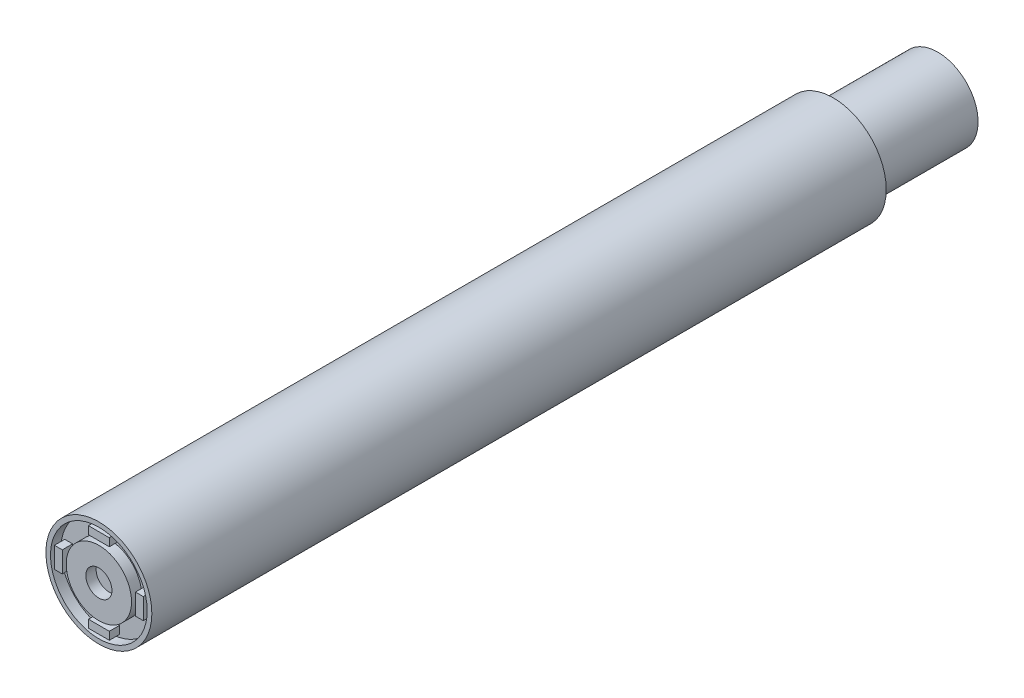
SolidWorks part; units mm, degrees
ref_plane "Front Plane" through (0, 0, 0) normal (0, 0, 1) x (1, 0, 0)
ref_plane "Top Plane" through (0, 0, 0) normal (0, 1, 0) x (1, 0, 0)
ref_plane "Right Plane" through (0, 0, 0) normal (1, 0, 0) x (0, 0, -1)
sketch "Sketch1" plane through (0, 0, 0) normal (0, 0, 1) x (1, 0, 0)
  circle A0 centre (0, 0) radius 2.575
extrude "Boss-Extrude1" add sketch "Sketch1" against normal blind 35.7
sketch "Sketch2" plane through (0, 0, 0) normal (0, 0, 1) x (1, 0, 0)
  circle A0 centre (0, 0) radius 2.35
extrude "Cut-Extrude1" cut sketch "Sketch2" against normal blind 0.5
sketch "Sketch5" plane through (0, 0, 0) normal (0, 0, 1) x (1, 0, 0)
  circle A0 centre (0, 0) radius 0.635
  circle A1 centre (0, 0) radius 1.5875
  dimension "D1" = 1.27
extrude "Boss-Extrude2" add sketch "Sketch5" against normal blind 0.508
sketch "Sketch6" plane through (0, 0, 0) normal (0, 0, 1) x (1, 0, 0)
  line L1 (-0.508, 1.778) -> (0.508, 1.778)
  line L2 (-0.508, 1.778) -> (-0.508, 2.159)
  line L3 (-0.508, 2.159) -> (0.508, 2.159)
  line L4 (0.508, 1.778) -> (0.508, 2.159)
  line L5 (-0.508, 1.778) -> (0.508, 2.159) construction
  line L6 (-0.508, 2.159) -> (0.508, 1.778) construction
  line L7 (-0.508, -2.159) -> (0.508, -2.159)
  line L8 (-0.508, -2.159) -> (-0.508, -1.778)
  line L9 (-0.508, -1.778) -> (0.508, -1.778)
  line L10 (0.508, -2.159) -> (0.508, -1.778)
  line L11 (-0.508, -2.159) -> (0.508, -1.778) construction
  line L12 (-0.508, -1.778) -> (0.508, -2.159) construction
  line L13 (-2.159, -0.508) -> (-1.778, -0.508)
  line L14 (-2.159, -0.508) -> (-2.159, 0.508)
  line L15 (-2.159, 0.508) -> (-1.778, 0.508)
  line L16 (-1.778, -0.508) -> (-1.778, 0.508)
  line L17 (-2.159, -0.508) -> (-1.778, 0.508) construction
  line L18 (-2.159, 0.508) -> (-1.778, -0.508) construction
  line L19 (1.778, -0.508) -> (2.159, -0.508)
  line L20 (1.778, -0.508) -> (1.778, 0.508)
  line L21 (1.778, 0.508) -> (2.159, 0.508)
  line L22 (2.159, -0.508) -> (2.159, 0.508)
  line L23 (1.778, -0.508) -> (2.159, 0.508) construction
  line L24 (1.778, 0.508) -> (2.159, -0.508) construction
  point P0 (0, 1.9685)
  point P8 (0, -1.9685)
  point P13 (-1.9685, 0)
  point P18 (1.9685, 0)
  dimension "D1" = 1.016
  dimension "D2" = 0.381
  dimension "D3" = 1.016
  dimension "D4" = 0.381
  dimension "D5" = 1.016
  dimension "D6" = 0.381
  dimension "D7" = 1.016
  dimension "D8" = 0.381
extrude "Boss-Extrude3" add sketch "Sketch6" against normal blind 0.508
ref_axis "Central Axis" through (0, 0, -35.7) along (0, 0, 1)
sketch "Sketch7" plane through (0, 0, -35.7) normal (0, 0, -1) x (-1, 0, 0)
  circle A0 centre (0, 0) radius 1.9588
extrude "Boss-Extrude4" add sketch "Sketch7" along normal blind 5.08
